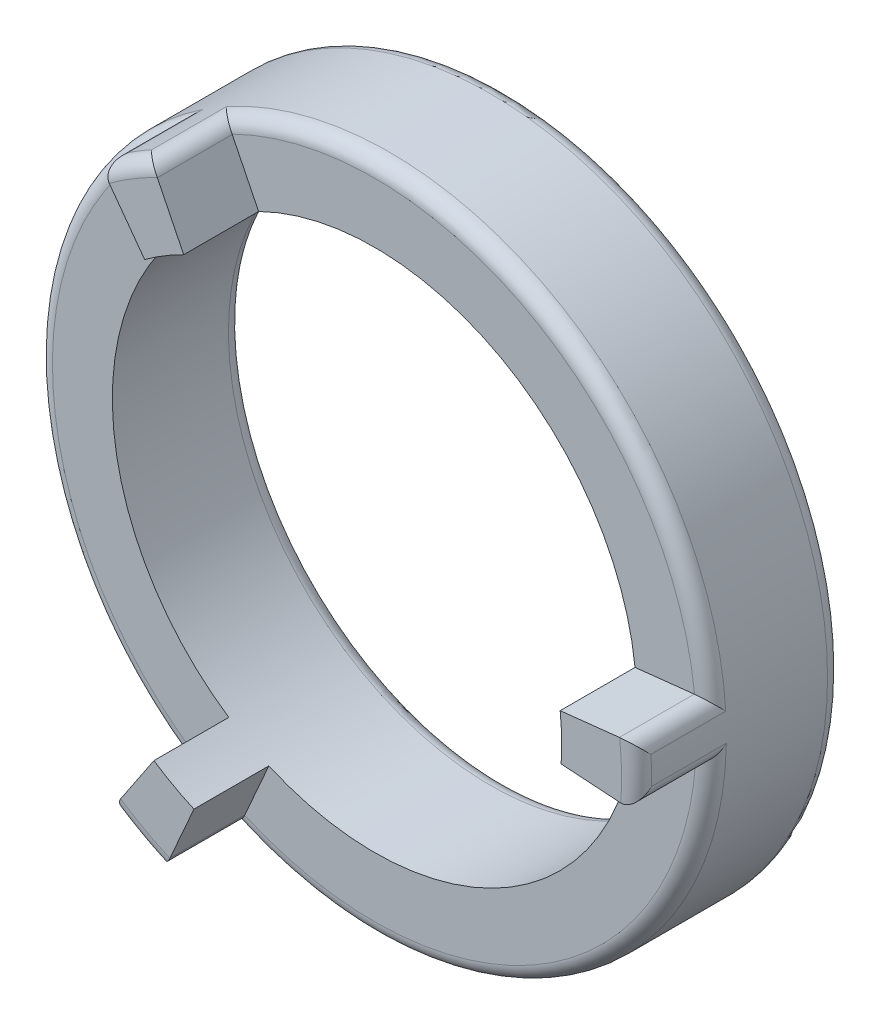
SolidWorks part; units mm, degrees
material "PC 高粘度"
ref_plane "前视基准面" through (0, 0, 0) normal (0, 0, 1) x (1, 0, 0)
ref_plane "上视基准面" through (0, 0, 0) normal (0, 1, 0) x (1, 0, 0)
ref_plane "右视基准面" through (0, 0, 0) normal (1, 0, 0) x (0, 0, -1)
sketch "草图1" plane through (0, 0, 0) normal (0, 0, 1) x (1, 0, 0)
  circle A0 centre (0, 0) radius 4.5
  dimension "D1" = 9
extrude "凸台-拉伸1" add sketch "草图1" along normal blind 1.75
sketch "草图2" plane through (0, 0, 0) normal (0, 0, -1) x (-1, 0, 0)
  circle A0 centre (0, 0) radius 3.5
extrude "切除-拉伸1" cut sketch "草图2" against normal blind 1.75
sketch "草图3" plane through (0, 0, 1.75) normal (0, 0, 1) x (1, 0, 0)
  line L0 (-1.5472, 3.1394) -> (-1.9893, 4.0364)
  line L1 (-2.0689, 2.8231) -> (-2.66, 3.6297)
  arc A0 (-1.9893, 4.0364) -> (-2.66, 3.6297) centre (0, 0) ccw
  arc A1 (-1.5472, 3.1394) -> (-2.0689, 2.8231) centre (0, 0) ccw
  dimension "D1" = 10
extrude "凸台-拉伸2" add sketch "草图3" along normal blind 1
ref_axis "基准轴1" through (0, 0, 2.75) along (0, 0, -1)
sketch "草图4" plane through (0, 0, 0) normal (-0.8066, -0.5911, 0) x (0, 0, 1)
  line L0 (2.45, 3.5) -> (2.45, 3.4538)
  line L2 (2.45, 3.4538) -> (2.45, 3.3307)
  line L3 (2.65, 4) -> (2.65, 3.5)
  line L4 (2.75, 3.5) -> (1.75, 3.5) construction
  line L5 (2.65, 3.4538) -> (2.65, 3.5)
  line L6 (2.45, 3.5) -> (2.45, 4)
  line L7 (2.45, 4) -> (2.65, 4)
  line L8 (2.45, 3.3307) -> (2.65, 3.3307)
  line L9 (2.65, 3.3307) -> (2.65, 3.4538)
pattern_circular "阵列(圆周)2" count 3 over 360 about axis through (0, 0, 2.75) along (0, 0, -1) of "凸台-拉伸2"
fillet "圆角1" radius 0.2 14 edges at (-2.501, -3.741, 2.25) (-2.1654, -3.9447, 2.75) (-1.8134, -4.1185, 2.25) (2.3335, -3.8477, 1.75) (4.4903, -0.2954, 2.25) (4.499, 0.097, 2.75) (4.4734, 0.4888, 2.25) (2.1654, 3.9447, 1.75) (-1.9893, 4.0364, 2.25) (-2.3335, 3.8477, 2.75) (-2.66, 3.6297, 2.25) (-4.499, -0.097, 1.75) (4.5, 0, 0) (-3.5, 0, 0)
